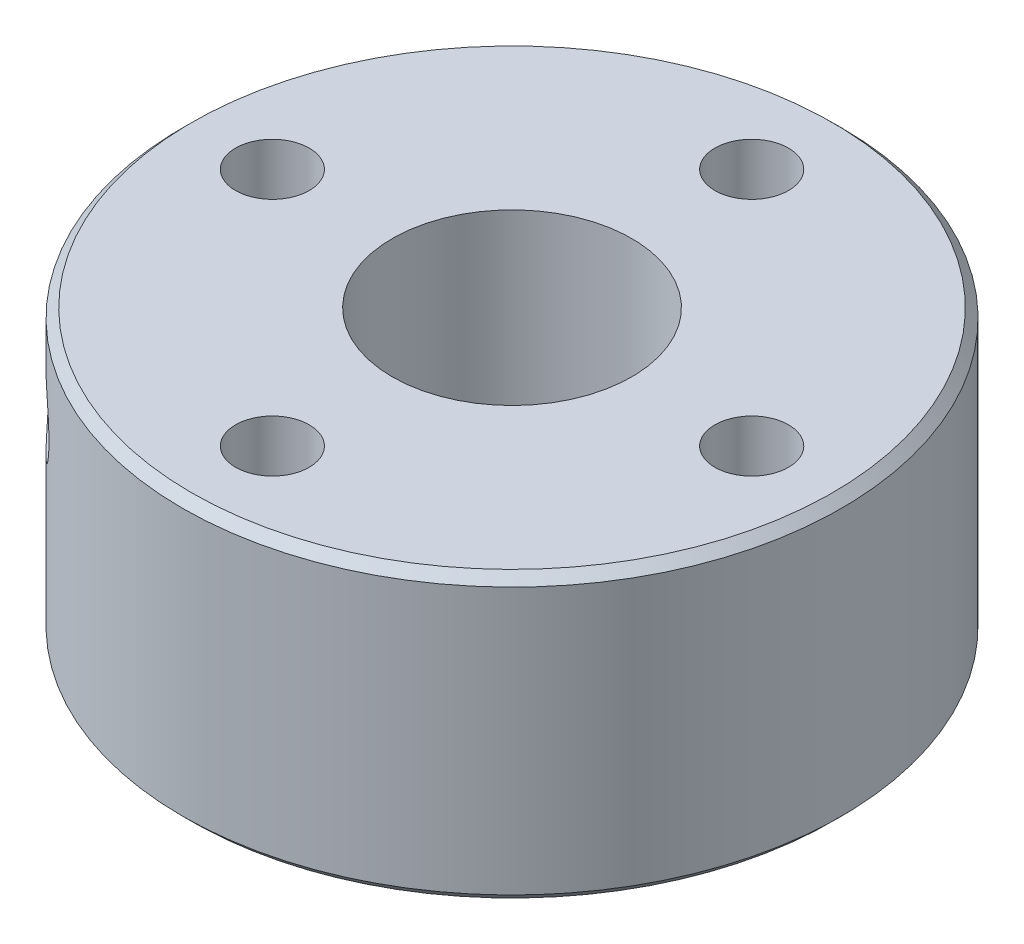
SolidWorks part; units mm, degrees
material "Lega 1060"
ref_plane "Piano frontale" through (0, 0, 0) normal (0, 0, 1) x (1, 0, 0)
ref_plane "Piano superiore" through (0, 0, 0) normal (0, 1, 0) x (1, 0, 0)
ref_plane "Piano destro" through (0, 0, 0) normal (1, 0, 0) x (0, 0, -1)
ref_plane "Piano1" through (0, 0, 0) normal (0, 0, -1) x (-1, 0, 0)
sketch "Schizzo1" plane through (0, 0, 0) normal (0, 0, -1) x (-1, 0, 0)
  line L0 (-11, 3.5) -> (0, 3.5)
  line L1 (0, 3.5) -> (0, 13)
  line L2 (0, 13) -> (-11, 13)
  line L3 (-11, 13) -> (-11, 3.5)
  line L4 (0, 3.5) -> (0, 13) construction
revolve "Rivoluzione1" add sketch "Schizzo1" angle 360 about L4 reverse direction yes
sketch "Schizzo2" plane through (0, 3.5, 0) normal (0, -1, 0) x (1, 0, 0)
  circle A0 centre (0, 0) radius 4.75
extrude "Estrusione-Estrusione1" add sketch "Schizzo2" along normal blind 3.5
hole_wizard "Foro per Vite M2-1" positions "Schizzo4" profile "Schizzo3" hole size "M2" standard "Ansi Metric"
sketch "Schizzo4" plane through (0, 13, 0) normal (0, 1, 0) x (1, 0, 0)
  point P0 (0, 8)
  point P1 (-8, 0)
  point P2 (0, -8)
  point P3 (8, 0)
sketch "Schizzo3" plane through (0, 13, -8) normal (1, 0, 0) x (0, 0, 1)
  line L0 (0, 0) -> (0, 13)
  line L1 (0, 13) -> (1.2295, 13)
  line L2 (1.2295, 13) -> (1.2295, 0)
  line L5 (1.2295, 0) -> (0, 0)
  line L11 (0, -6.35) -> (0, 107.95) construction
  dimension "Thru Hole Dia." = 2.459
  dimension "Thru Hole Depth" = 13
hole_wizard "Foro lamato per Vite M3.5 a testa esagonale-1" positions "Schizzo6" profile "Schizzo5" counterbore size "M3.5" standard "Ansi Metric"
sketch "Schizzo6" plane through (0, 13, 0) normal (0, 1, 0) x (1, 0, 0)
  point P0 (0, 0)
sketch "Schizzo5" plane through (0, 13, 0) normal (1, 0, 0) x (0, 0, 1)
  line L0 (0, 0) -> (0, 13)
  line L1 (0, 13) -> (2, 13)
  line L3 (2, 13) -> (2, 8.5)
  line L4 (2, 8.5) -> (4, 8.5)
  line L5 (4, 8.5) -> (4, 0)
  line L7 (4, 0) -> (0, 0)
  line L11 (0, -6.35) -> (0, 107.95) construction
  dimension "Thru Hole Dia." = 4
  dimension "Thru Hole Depth" = 13
  dimension "C'Bore Dia." = 8
  dimension "C'Bore Depth" = 8.5
ref_plane "Piano2" through (-2.6915, 0, 2.6915) normal (0.7071, 0, -0.7071) x (-0.7071, 0, -0.7071)
hole_wizard "Foro per Vite M2-2" positions "Schizzo8" profile "Schizzo7" hole size "M2" standard "Ansi Metric"
sketch "Schizzo8" plane through (-2.6915, 0, 2.6915) normal (0.7071, 0, -0.7071) x (-0.7071, 0, -0.7071)
  point P0 (0, 10)
sketch "Schizzo7" plane through (-2.6915, 10, 2.6915) normal (0, 1, 0) x (-0.7071, 0, -0.7071)
  line L0 (0, 0) -> (0, 11.75)
  line L1 (0, 11.75) -> (1.2295, 11.75)
  line L2 (1.2295, 11.75) -> (1.2295, 0)
  line L5 (1.2295, 0) -> (0, 0)
  line L11 (0, -6.35) -> (0, 107.95) construction
  dimension "Thru Hole Dia." = 2.459
  dimension "Thru Hole Depth" = 11.75
chamfer "Smusso1" distance 0.3 angle 45 3 edges at (0, 0, -4.75) (0, 3.5, 11) (0, 13, 11)
